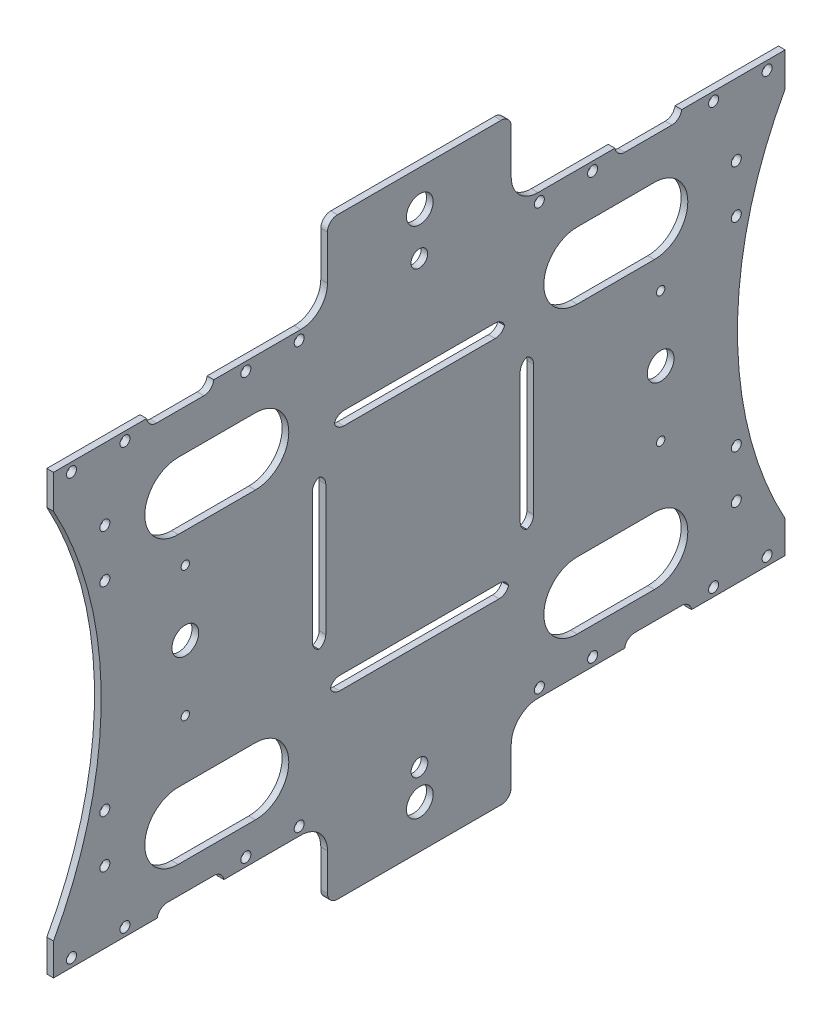
SolidWorks part; units mm, degrees
ref_plane "前视基准面" through (0, 0, 0) normal (0, 0, 1) x (1, 0, 0)
ref_plane "上视基准面" through (0, 0, 0) normal (0, 1, 0) x (1, 0, 0)
ref_plane "右视基准面" through (0, 0, 0) normal (1, 0, 0) x (0, 0, -1)
sketch "Sketch1" plane through (0, 0, 0) normal (1, 0, 0) x (0, 0, -1)
  line L0 (36.3378, 137.3317) -> (36.3378, 77.1748) construction
  line L1 (-182.6622, 87.2892) -> (36.3378, 87.2892)
  line L2 (-182.6622, 87.2892) -> (-182.6622, -43.8053)
  line L3 (-182.6622, -43.8053) -> (36.3378, -43.8053)
  line L4 (36.3378, 87.2892) -> (36.3378, -43.8053)
  line L5 (-182.6622, 87.2892) -> (36.3378, -43.8053) construction
  line L6 (-182.6622, -43.8053) -> (36.3378, 87.2892) construction
  line L7 (-182.6622, 137.3317) -> (-182.6622, 77.1748) construction
  line L8 (-182.6622, -94.3758) -> (-182.6622, -34.2189) construction
  point P0 (-73.1622, 21.742)
extrude "Boss-Extrude1" add sketch "Sketch1" along normal blind 2
sketch "Sketch2" plane through (2, 0, 0) normal (1, 0, 0) x (0, 0, -1)
  line L0 (-167.1842, 84.6899) -> (-189.8208, 84.6899) construction
  line L1 (-87.1347, 86.162) -> (-87.1347, 101.7527) construction
  line L2 (-180.2416, -41.2557) -> (-183.5915, -41.2557) construction
  line L3 (-182.1347, 21.162) -> (-173.3707, 21.162) construction
  circle A0 centre (-177.2782, 84.6899) radius 1.5
  circle A1 centre (-161.2773, 84.6899) radius 1.5
  circle A2 centre (14.9073, 84.6899) radius 1.5
  circle A3 centre (30.9402, 84.6899) radius 1.5
  circle A4 centre (-125.0909, 84.6899) radius 1.5
  circle A5 centre (-109.1212, 84.6899) radius 1.5
  circle A6 centre (-37.2397, 84.6899) radius 1.5
  circle A7 centre (-21.2903, 84.6899) radius 1.5
  circle A8 centre (-177.2782, -41.2557) radius 1.5
  circle A9 centre (-161.2773, -41.2557) radius 1.5
  circle A10 centre (-125.0909, -41.2557) radius 1.5
  circle A11 centre (-109.1212, -41.2557) radius 1.5
  circle A12 centre (-21.2903, -41.2557) radius 1.5
  circle A13 centre (-37.2397, -41.2557) radius 1.5
  circle A14 centre (14.9073, -41.2557) radius 1.5
  circle A15 centre (30.9402, -41.2557) radius 1.5
extrude "Cut-Extrude1" cut sketch "Sketch2" against normal blind 2
sketch "Sketch3" plane through (2, 0, 0) normal (1, 0, 0) x (0, 0, -1)
  line L0 (36.3378, 87.2892) -> (-182.6622, 87.2892) construction
  line L1 (-154.7837, 89.9448) -> (-134.683, 89.9448)
  line L2 (-154.7837, 89.9448) -> (-154.7837, 84.6337)
  line L3 (-154.7837, 84.6337) -> (-134.683, 84.6337)
  line L4 (-134.683, 89.9448) -> (-134.683, 84.6337)
  line L5 (-154.7837, 89.9448) -> (-134.683, 84.6337) construction
  line L6 (-154.7837, 84.6337) -> (-134.683, 89.9448) construction
  line L7 (-182.6622, -43.8053) -> (36.3378, -43.8053) construction
  line L8 (-14.6371, 89.8214) -> (5.3843, 89.8214)
  line L9 (-14.6371, 89.8214) -> (-14.6371, 84.7571)
  line L10 (-14.6371, 84.7571) -> (5.3843, 84.7571)
  line L11 (5.3843, 89.8214) -> (5.3843, 84.7571)
  line L12 (-14.6371, 89.8214) -> (5.3843, 84.7571) construction
  line L13 (-14.6371, 84.7571) -> (5.3843, 89.8214) construction
  line L14 (-151.6036, -41.2639) -> (-131.6627, -41.2639)
  line L15 (-151.6036, -41.2639) -> (-151.6036, -46.3467)
  line L16 (-151.6036, -46.3467) -> (-131.6627, -46.3467)
  line L17 (-131.6627, -41.2639) -> (-131.6627, -46.3467)
  line L18 (-151.6036, -41.2639) -> (-131.6627, -46.3467) construction
  line L19 (-151.6036, -46.3467) -> (-131.6627, -41.2639) construction
  line L21 (-11.6994, -41.2643) -> (8.3072, -41.2643)
  line L22 (-11.6994, -41.2643) -> (-11.6994, -46.3463)
  line L23 (-11.6994, -46.3463) -> (8.3072, -46.3463)
  line L24 (8.3072, -41.2643) -> (8.3072, -46.3463)
  line L25 (-11.6994, -41.2643) -> (8.3072, -46.3463) construction
  line L26 (-11.6994, -46.3463) -> (8.3072, -41.2643) construction
  point P0 (-144.7333, 87.2892)
  point P7 (-4.6264, 87.2892)
  point P12 (-141.6332, -43.8053)
  point P19 (-1.6961, -43.8053)
extrude "Cut-Extrude2" cut sketch "Sketch3" against normal blind 2
fillet "Fillet1" radius 3 8 edges at (1, 84.6337, 154.7837) (1, 84.6337, 134.683) (1, 84.7571, -5.3843) (1, 84.7571, 14.6371) (1, -41.2643, 11.6994) (1, -41.2643, -8.3072) (1, -41.2639, 131.6627) (1, -41.2639, 151.6036)
sketch "Sketch4" plane through (2, 0, 0) normal (1, 0, 0) x (0, 0, -1)
  line L2 (-182.6622, 21.742) -> (-175.2516, 21.742) construction
  line L5 (21.7084, -22.3962) -> (-167.297, -22.3962) construction
  line L6 (21.7084, -22.3962) -> (21.7084, 65.8802) construction
  line L7 (21.7084, 65.8802) -> (-167.297, 65.8802) construction
  line L8 (-167.297, -22.3962) -> (-167.297, 65.8802) construction
  line L9 (21.7084, -22.3962) -> (-167.297, 65.8802) construction
  line L10 (21.7084, 65.8802) -> (-167.297, -22.3962) construction
  line L11 (21.7084, -8.0311) -> (-167.297, -8.0311) construction
  line L12 (21.7084, -8.0311) -> (21.7084, 51.515) construction
  line L13 (21.7084, 51.515) -> (-167.297, 51.515) construction
  line L14 (-167.297, -8.0311) -> (-167.297, 51.515) construction
  line L15 (21.7084, -8.0311) -> (-167.297, 51.515) construction
  line L16 (21.7084, 51.515) -> (-167.297, -8.0311) construction
  circle A0 centre (-167.297, 65.8802) radius 1.5
  circle A1 centre (-167.297, 51.515) radius 1.5
  circle A2 centre (-167.297, -8.0311) radius 1.5
  circle A3 centre (-167.297, -22.3962) radius 1.5
  circle A4 centre (21.7084, 65.8802) radius 1.5
  circle A5 centre (21.7084, 51.515) radius 1.5
  circle A6 centre (21.7084, -8.0311) radius 1.5
  circle A7 centre (21.7084, -22.3962) radius 1.5
  point P2 (-72.7943, 21.742)
  point P9 (-72.7943, 21.742)
extrude "Cut-Extrude3" cut sketch "Sketch4" against normal blind 2
sketch "Sketch5" plane through (2, 0, 0) normal (1, 0, 0) x (0, 0, -1)
  line L0 (-72.0696, 114.1679) -> (-72.0696, 121.7669) construction
  line L1 (-182.6622, 77.1748) -> (-182.6622, -34.2189)
  line L3 (24.075, -1.0194) -> (-25.925, 48.9806) construction
  line L4 (24.075, 48.9806) -> (-25.925, -1.0194) construction
  line L9 (-25.925, 48.9806) -> (-25.925, -1.0194) construction
  line L10 (24.075, -1.0194) -> (-25.925, -1.0194) construction
  line L15 (24.075, 48.9806) -> (24.075, -1.0194) construction
  line L16 (24.075, 48.9806) -> (-25.925, 48.9806) construction
  line L21 (3.2791, 4.4806) -> (-5.1291, 43.4806) construction
  line L22 (3.2791, 43.4806) -> (-5.1291, 4.4806) construction
  line L27 (-5.1291, 43.4806) -> (-5.1291, 4.4806) construction
  line L28 (3.2791, 4.4806) -> (-5.1291, 4.4806) construction
  line L33 (3.2791, 43.4806) -> (3.2791, 4.4806) construction
  line L34 (3.2791, 43.4806) -> (-5.1291, 43.4806) construction
  line L43 (-147.4182, 43.4806) -> (-139.01, 43.4806) construction
  line L46 (36.3378, 77.1748) -> (36.3378, -34.2189)
  line L49 (-147.4182, 43.4806) -> (-147.4182, 4.4806) construction
  line L52 (-25.8971, 62.4969) -> (-2.7991, 62.4969) construction
  line L53 (-25.8971, 72.4969) -> (-2.7991, 72.4969)
  line L54 (-25.8971, 52.4969) -> (-2.7991, 52.4969)
  line L55 (-25.8971, -23.0278) -> (-2.7991, -23.0278) construction
  line L56 (-25.8971, -33.0278) -> (-2.7991, -33.0278)
  line L57 (-25.8971, -13.0278) -> (-2.7991, -13.0278)
  line L58 (-147.4182, 4.4806) -> (-139.01, 4.4806) construction
  line L69 (-139.01, 43.4806) -> (-139.01, 4.4806) construction
  line L72 (-122.2378, 62.4969) -> (-145.3359, 62.4969) construction
  line L73 (-122.2378, 72.4969) -> (-145.3359, 72.4969)
  line L74 (-122.2378, 52.4969) -> (-145.3359, 52.4969)
  line L75 (-122.2378, -23.0278) -> (-145.3359, -23.0278) construction
  line L76 (-122.2378, -33.0278) -> (-145.3359, -33.0278)
  line L77 (-122.2378, -13.0278) -> (-145.3359, -13.0278)
  line L78 (-147.4182, 43.4806) -> (-139.01, 4.4806) construction
  line L79 (-147.4182, 4.4806) -> (-139.01, 43.4806) construction
  line L80 (36.3378, -43.8053) -> (36.3378, 87.2892) construction
  line L81 (-103.1719, 16.6727) -> (-40.9673, 16.6727) construction
  line L82 (-103.1719, 16.6727) -> (-103.1719, 31.2885) construction
  line L83 (-103.1719, 31.2885) -> (-40.9673, 31.2885) construction
  line L84 (-40.9673, 16.6727) -> (-40.9673, 31.2885) construction
  line L85 (-103.1719, 16.6727) -> (-40.9673, 31.2885) construction
  line L86 (-103.1719, 31.2885) -> (-40.9673, 16.6727) construction
  line L87 (-105.1719, 46.4806) -> (-101.1719, 46.4806)
  line L88 (-105.1719, 46.4806) -> (-105.1719, 1.4806)
  line L89 (-105.1719, 1.4806) -> (-101.1719, 1.4806)
  line L90 (-101.1719, 46.4806) -> (-101.1719, 1.4806)
  line L91 (-105.1719, 46.4806) -> (-101.1719, 1.4806) construction
  line L92 (-105.1719, 1.4806) -> (-101.1719, 46.4806) construction
  line L93 (-38.9673, 46.4806) -> (-42.9673, 46.4806)
  line L94 (-38.9673, 46.4806) -> (-38.9673, 1.4806)
  line L95 (-38.9673, 1.4806) -> (-42.9673, 1.4806)
  line L96 (-42.9673, 46.4806) -> (-42.9673, 1.4806)
  line L97 (-38.9673, 46.4806) -> (-42.9673, 1.4806) construction
  line L98 (-38.9673, 1.4806) -> (-42.9673, 46.4806) construction
  line L100 (-168.2141, 48.9806) -> (-118.2141, 48.9806) construction
  line L101 (-168.2141, 48.9806) -> (-168.2141, -1.0194) construction
  line L102 (-168.2141, -1.0194) -> (-118.2141, -1.0194) construction
  line L103 (-118.2141, 48.9806) -> (-118.2141, -1.0194) construction
  line L104 (-168.2141, 48.9806) -> (-118.2141, -1.0194) construction
  line L105 (-168.2141, -1.0194) -> (-118.2141, 48.9806) construction
  line L107 (-78.733, 105.9002) -> (-78.733, -17.7673) construction
  line L109 (-68.6738, 45.2562) -> (-68.6738, -17.7673) construction
  line L110 (-78.733, 105.9002) -> (-68.6738, -17.7673) construction
  line L111 (-78.733, -17.7673) -> (-68.6738, 45.2562) construction
  arc A10 (-25.8971, 72.4969) -> (-25.8971, 52.4969) centre (-25.8971, 62.4969) ccw
  arc A11 (-2.7991, 52.4969) -> (-2.7991, 72.4969) centre (-2.7991, 62.4969) ccw
  arc A12 (-25.8971, -33.0278) -> (-25.8971, -13.0278) centre (-25.8971, -23.0278) cw
  arc A13 (-2.7991, -13.0278) -> (-2.7991, -33.0278) centre (-2.7991, -23.0278) cw
  arc A27 (-122.2378, 72.4969) -> (-122.2378, 52.4969) centre (-122.2378, 62.4969) cw
  arc A28 (-145.3359, 52.4969) -> (-145.3359, 72.4969) centre (-145.3359, 62.4969) cw
  arc A29 (-122.2378, -33.0278) -> (-122.2378, -13.0278) centre (-122.2378, -23.0278) ccw
  arc A30 (-145.3359, -13.0278) -> (-145.3359, -33.0278) centre (-145.3359, -23.0278) ccw
  arc A47 (-182.6622, 77.1748) -> (-182.6622, -34.2189) centre (-284.1488, 21.478) cw
  arc A48 (36.3378, 77.1748) -> (36.3378, -34.2189) centre (137.8244, 21.478) ccw
  circle A52 centre (-143.2141, 43.4806) radius 1.25
  circle A53 centre (-143.2141, 4.4806) radius 1.25
  circle A54 centre (-143.2141, 23.9806) radius 4
  circle A55 centre (-0.925, 23.9806) radius 4
  circle A56 centre (-0.925, 4.4806) radius 1.25
  circle A57 centre (-0.925, 43.4806) radius 1.25
  point P20 (-72.0696, 23.9806)
  point P38 (-143.2141, 23.9806)
  point P39 (-143.2141, 23.9806)
  point P44 (-143.2141, 23.9806)
  point P45 (-143.2141, 23.9806)
  point P56 (-103.1719, 23.9806)
  point P61 (-40.9673, 23.9806)
  point P64 (-14.3481, 62.4969)
  point P71 (-14.3481, -23.0278)
  point P112 (-133.7868, 62.4969)
  point P119 (-133.7868, -23.0278)
  dimension "D6" = 8
  dimension "D7" = 0
  dimension "D5" = 0
  dimension "D1" = 45
  dimension "D3" = 4
  dimension "D4" = 4
  dimension "D9" = 50
  dimension "D10" = 50
extrude "Cut-Extrude4" cut sketch "Sketch5" against normal blind 10
sketch "Sketch6" plane through (2, 0, 0) normal (1, 0, 0) x (0, 0, -1)
  line L0 (-182.6622, 22.8188) -> (-173.3682, 22.8188) construction
  line L1 (-45.6622, 77.1748) -> (-45.6622, 139.7191) construction
  line L3 (-100.6622, 111.5484) -> (-45.6622, 111.5484)
  line L4 (-100.6622, 111.5484) -> (-100.6622, 57.0915)
  line L5 (-100.6622, 57.0915) -> (-45.6622, 57.0915)
  line L6 (-45.6622, 111.5484) -> (-45.6622, 57.0915)
  line L11 (-45.6622, -65.9107) -> (-45.6622, -11.4538)
  line L12 (-100.6622, -11.4538) -> (-45.6622, -11.4538)
  line L13 (-100.6622, -65.9107) -> (-100.6622, -11.4538)
  line L14 (-100.6622, -65.9107) -> (-45.6622, -65.9107)
  line L16 (-14.6371, 87.2892) -> (-134.683, 87.2892) construction
  line L17 (-100.6622, 77.1748) -> (-100.6622, 139.7191) construction
  point P1 (-74.66, 87.2892)
extrude "Boss-Extrude2" add sketch "Sketch6" against normal up to surface (2 mm away) up to face at (0, 62.4969, 14.3481)
fillet "Fillet2" radius 8 4 edges at (1, 87.2892, 100.6622) (1, 87.2892, 45.6622) (1, -43.8053, 45.6622) (1, -43.8053, 100.6622)
fillet "Fillet3" radius 3 4 edges at (1, 111.5484, 100.6622) (1, 111.5484, 45.6622) (1, -65.9107, 100.6622) (1, -65.9107, 45.6622)
sketch "Sketch7" plane through (2, 0, 0) normal (1, 0, 0) x (0, 0, -1)
  line L0 (-73.0166, 108.9662) -> (-73.0166, 124.2819) construction
  circle A0 centre (-73.0166, 100.6646) radius 4
  circle A1 centre (-73.0166, -52.9913) radius 4
extrude "Cut-Extrude5" cut sketch "Sketch7" against normal blind 10
sketch "Sketch8" plane through (2, 0, 0) normal (1, 0, 0) x (0, 0, -1)
  line L0 (-73.13, 25.6399) -> (-73.13, 20.0748) construction
  line L2 (-75.6622, 87.9806) -> (-70.6622, 87.9806) construction
  line L3 (-75.6622, 87.9806) -> (-75.6622, -40.0194) construction
  line L4 (-75.6622, -40.0194) -> (-70.6622, -40.0194) construction
  line L5 (-70.6622, 87.9806) -> (-70.6622, -40.0194) construction
  line L6 (-75.6622, 87.9806) -> (-70.6622, -40.0194) construction
  line L7 (-75.6622, -40.0194) -> (-70.6622, 87.9806) construction
  line L8 (-85.1622, 46.4806) -> (-61.1622, 46.4806) construction
  line L9 (-88.1622, 43.4806) -> (-88.1622, 4.4806) construction
  line L10 (-85.1622, 1.4806) -> (-61.1622, 1.4806) construction
  line L11 (-58.1622, 43.4806) -> (-58.1622, 4.4806) construction
  line L12 (-88.1622, 46.4806) -> (-58.1622, 1.4806) construction
  line L13 (-88.1622, 1.4806) -> (-58.1622, 46.4806) construction
  line L14 (-98.7887, 59.8689) -> (-47.4714, 59.8689)
  line L15 (-98.7887, 59.8689) -> (-98.7887, 55.8689)
  line L16 (-98.7887, 55.8689) -> (-47.4714, 55.8689)
  line L17 (-47.4714, 59.8689) -> (-47.4714, 55.8689)
  line L18 (-98.7887, 59.8689) -> (-47.4714, 55.8689) construction
  line L19 (-98.7887, 55.8689) -> (-47.4714, 59.8689) construction
  line L20 (-99.999, -8.2007) -> (-46.2611, -8.2007)
  line L21 (-99.999, -8.2007) -> (-99.999, -12.2007)
  line L22 (-99.999, -12.2007) -> (-46.2611, -12.2007)
  line L23 (-46.2611, -8.2007) -> (-46.2611, -12.2007)
  line L24 (-99.999, -8.2007) -> (-46.2611, -12.2007) construction
  line L25 (-99.999, -12.2007) -> (-46.2611, -8.2007) construction
  circle A1 centre (-73.1622, 87.9806) radius 2.5
  circle A2 centre (-73.13, -43.9252) radius 2.5
  arc A3 (-88.1622, 4.4806) -> (-85.1622, 1.4806) centre (-85.1622, 4.4806) ccw construction
  arc A4 (-61.1622, 1.4806) -> (-58.1622, 4.4806) centre (-61.1622, 4.4806) ccw construction
  arc A5 (-61.1622, 46.4806) -> (-58.1622, 43.4806) centre (-61.1622, 43.4806) cw construction
  arc A6 (-85.1622, 46.4806) -> (-88.1622, 43.4806) centre (-85.1622, 43.4806) ccw construction
  point P1 (-73.1622, 23.9806)
  point P4 (-73.13, 57.8689)
  point P13 (-73.1622, 23.9806)
  point P34 (-73.13, -10.2007)
  dimension "D2" = 30
  dimension "D4" = 3
  dimension "D1" = 128
  dimension "D3" = 45
  dimension "D5" = 4
  dimension "D6" = 4
extrude "Cut-Extrude6" cut sketch "Sketch8" against normal blind 3
fillet "Fillet4" radius 3 16 edges at (1, 46.4806, 42.9673) (1, 46.4806, 38.9673) (1, 1.4806, 42.9673) (1, 1.4806, 38.9673) (1, 1.4806, 101.1719) (1, 1.4806, 105.1719) (1, 46.4806, 101.1719) (1, 46.4806, 105.1719) (1, 59.8689, 98.7887) (1, 55.8689, 98.7887) (1, 59.8689, 47.4714) (1, 55.8689, 47.4714) (1, -12.2007, 46.2611) (1, -8.2007, 46.2611) (1, -12.2007, 99.999) (1, -8.2007, 99.999)
